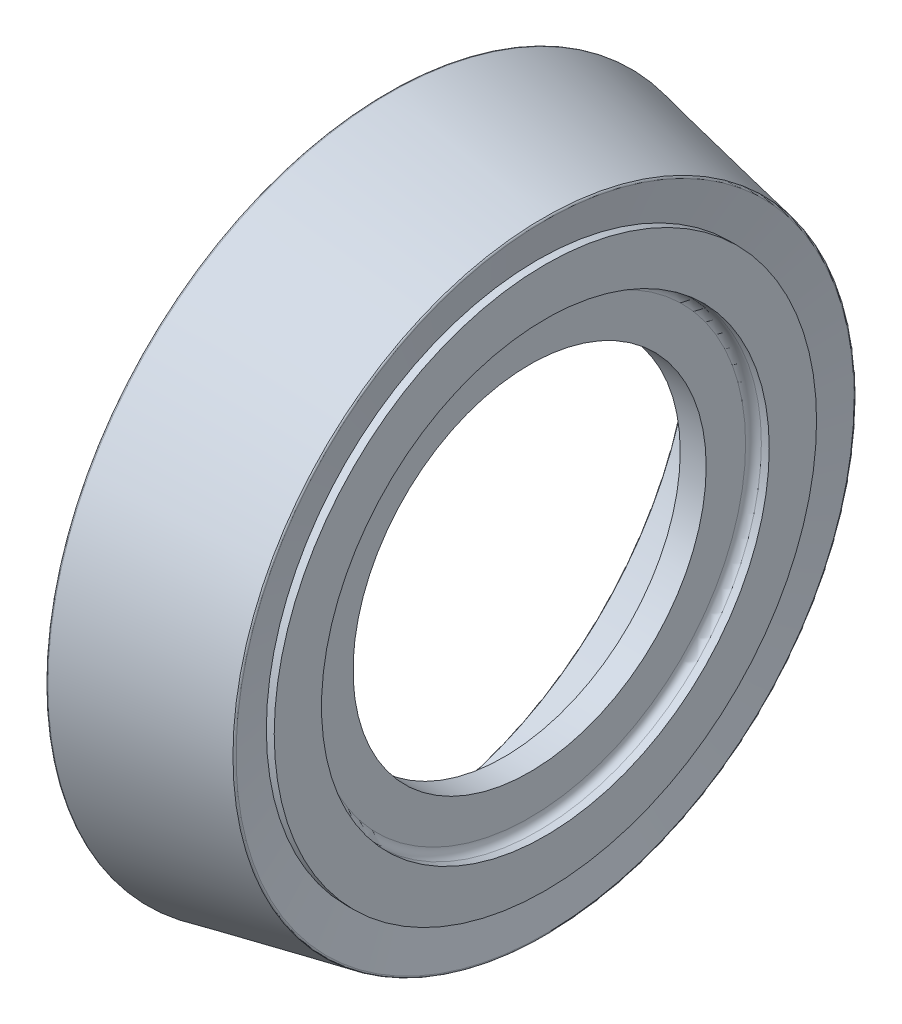
SolidWorks part; units mm, degrees
ref_plane "Płaszczyzna przednia" through (0, 0, 0) normal (0, 0, 1) x (1, 0, 0)
ref_plane "Płaszczyzna górna" through (0, 0, 0) normal (0, 1, 0) x (1, 0, 0)
ref_plane "Płaszczyzna prawa" through (0, 0, 0) normal (1, 0, 0) x (0, 0, -1)
sketch "Szkic1" plane through (0, 0, 0) normal (0, 0, 1) x (1, 0, 0)
  line L0 (1, 2.5) -> (1, 5.5)
  line L1 (1, 5.5) -> (0.5, 5.5)
  line L2 (0.5, 5.5) -> (0.9804, 7.9019)
  line L3 (1, 2.5) -> (0.5, 2.5)
  line L4 (0, 2) -> (0, -0.5)
  line L5 (-9, 7.582) -> (-9, 9.878)
  line L6 (0.9019, 8.0196) -> (-8.8804, 9.9761)
  line L7 (-8.9196, 7.4839) -> (-1.6456, 6.0291)
  line L8 (-1.6456, 6.0291) -> (-1.6456, -0.5)
  line L9 (-1.6456, -0.5) -> (0, -0.5)
  line L11 (0, -11.7) -> (-1.6456, -11.7)
  arc A0 (0, 2) -> (0.5, 2.5) centre (0.5, 2) cw
  arc A1 (0.9804, 7.9019) -> (0.9019, 8.0196) centre (0.8823, 7.9216) ccw
  arc A2 (-9, 7.582) -> (-8.9196, 7.4839) centre (-8.9, 7.582) ccw
  arc A3 (-8.8804, 9.9761) -> (-9, 9.878) centre (-8.9, 9.878) ccw
  point P12 (0, 2.5)
  point P15 (1, 8)
  point P18 (-9, 7.5)
  point P22 (-9, 10)
  dimension "D9" = 0.5
  dimension "D10" = 0.1
  dimension "D11" = 0.1
  dimension "D12" = 1.6456
  dimension "D1" = 3
  dimension "D2" = 1
  dimension "D3" = 3
  dimension "D4" = 0.5
  dimension "D5" = 2.5
  dimension "D6" = 10
  dimension "D7" = 2
  dimension "D8" = 7.5
  dimension "D13" = 2.5
  dimension "D14" = 3
  dimension "D15" = 1
  dimension "D16" = 11.2
  dimension "D17" = 1.6456
revolve "Obrót1" add sketch "Szkic1" angle 360 about L11 region at (0.75, 2.6448, 0)
